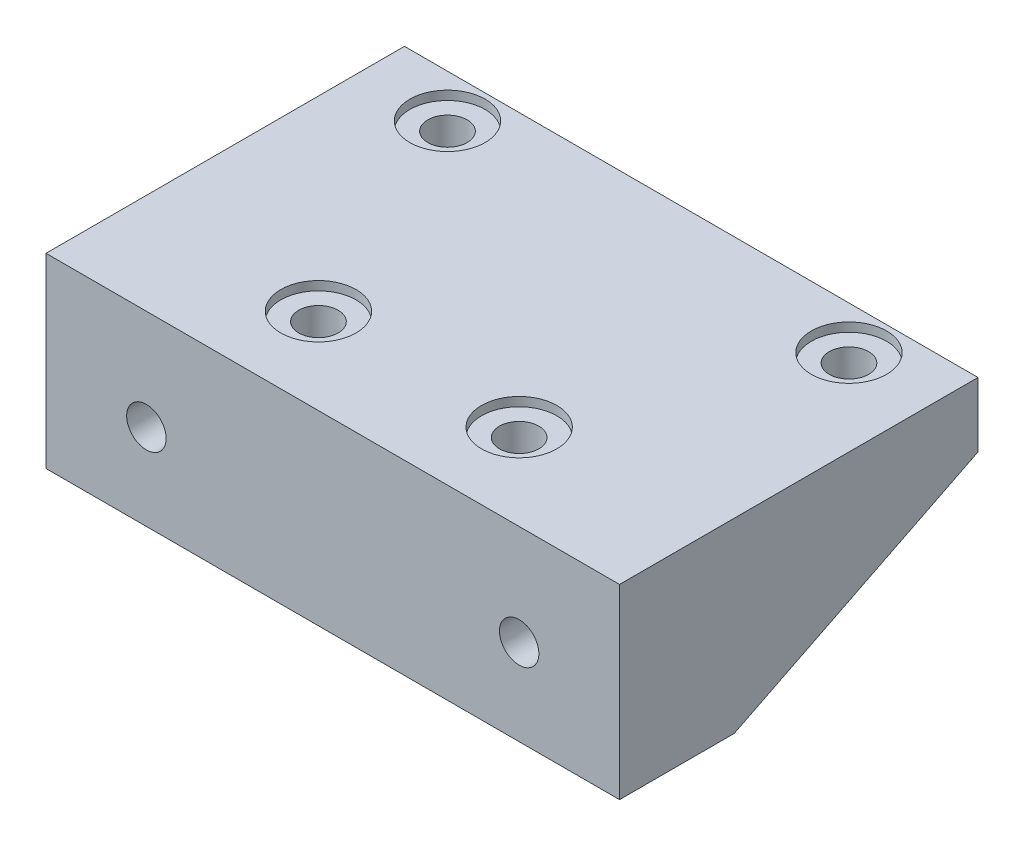
SolidWorks part; units mm, degrees
material "6061-T6 (SS)"
ref_plane "Front Plane" through (0, 0, 0) normal (0, 0, 1) x (1, 0, 0)
ref_plane "Top Plane" through (0, 0, 0) normal (0, 1, 0) x (1, 0, 0)
ref_plane "Right Plane" through (0, 0, 0) normal (1, 0, 0) x (0, 0, -1)
sketch "Sketch1" plane through (0, 0, 0) normal (0, 0, 1) x (1, 0, 0)
  line L1 (0, 0) -> (68, 0)
  line L2 (0, 0) -> (0, 26)
  line L3 (0, 26) -> (68, 26)
  line L4 (68, 0) -> (68, 26)
  dimension "D1" = 68
  dimension "D2" = 26
extrude "Boss-Extrude1" add sketch "Sketch1" along normal blind 6
sketch "Sketch2" plane through (0, 0, 6) normal (0, 0, 1) x (1, 0, 0)
  line L0 (68, 26) -> (0, 26) construction
  line L1 (-6, 26) -> (74, 26)
  line L2 (-6, 26) -> (-6, 20)
  line L3 (-6, 20) -> (74, 20)
  line L4 (74, 26) -> (74, 20)
  line L5 (34, 0) -> (34, 20) construction
  line L6 (0, 0) -> (68, 0) construction
  dimension "D1" = 6
  dimension "D2" = 80
extrude "Boss-Extrude2" add sketch "Sketch2" against normal blind 50
sketch "Sketch3" plane through (0, 0, 0) normal (0, 0, -1) x (-1, 0, 0)
  line L0 (-68, 0) -> (-68, 20) construction
  line L1 (0, 20) -> (0, 0) construction
  line L2 (-60, 12) -> (-8, 12) construction
  line L4 (-68, 20) -> (0, 20) construction
  point P0 (-60, 12)
  point P2 (-8, 12)
  dimension "D1" = 8
  dimension "D2" = 8
  dimension "D3" = 8
hole_wizard "M5 Clearance Hole1" positions "Sketch3" profile "Sketch4" hole size "M5" standard "DIN"
sketch "Sketch4" plane through (60, 12, 0) normal (1, 0, 0) x (0, 1, 0)
  line L0 (0, 0) -> (0, 11.6524)
  line L1 (0, 11.6524) -> (2.75, 10)
  line L2 (2.75, 10) -> (2.75, 0)
  line L5 (2.75, 0) -> (0, 0)
  line L10 (0, 11.6524) -> (-2.75, 10) construction
  line L11 (0, -6.35) -> (0, 107.95) construction
  dimension "Hole Dia." = 5.5
  dimension "Hole Depth" = 10
  dimension "Drill Angle" = 118
sketch "Sketch5" plane through (74, 0, 0) normal (1, 0, 0) x (0, 0, -1)
  line L0 (-6, 0) -> (10, 0)
  line L2 (44, 20) -> (-6, 20)
  line L3 (-6, 20) -> (-6, 0)
  line L4 (44, 20) -> (44, 17)
  line L5 (44, 17) -> (10, 0)
  dimension "D1" = 16
  dimension "D2" = 3
extrude "Boss-Extrude3" add sketch "Sketch5" against normal up to surface (6 mm away) up to face at (68, 10, 3)
extrude "Boss-Extrude4" add sketch "Sketch5<2>" along normal up to surface (-74 mm away) from surface up to face at (0, 10, 3) starting at face at (-6, 23, -19)
sketch "Sketch5<2>" plane through (74, 0, 0) normal (1, 0, 0) x (0, 0, -1) same geometry as "Sketch5"
sketch "Sketch6" plane through (0, 20, 0) normal (0, -1, 0) x (-1, 0, 0)
  line L1 (0, 0) -> (0, 44) construction
  line L2 (-62, 38) -> (-6, 38) construction
  line L4 (0, 44) -> (-68, 44) construction
  line L5 (-20, 6) -> (-48, 6) construction
  line L7 (-34, 6) -> (-34, 0) construction
  line L8 (-68, 0) -> (0, 0) construction
  line L9 (-68, 10) -> (-68, 44) construction
  point P0 (-48, 6)
  point P2 (-20, 6)
  point P4 (-62, 38)
  point P6 (-6, 38)
  dimension "D2" = 6
  dimension "D3" = 6
  dimension "D4" = 28
  dimension "D5" = 6
  dimension "D1" = 6
hole_wizard "M5 Clearance Hole2" positions "Sketch6" profile "Sketch7" hole size "M5" standard "DIN"
sketch "Sketch7" plane through (48, 20, -6) normal (1, 0, 0) x (0, 0, -1)
  line L0 (0, 0) -> (0, 11.6524)
  line L1 (0, 11.6524) -> (2.75, 10)
  line L2 (2.75, 10) -> (2.75, 0)
  line L5 (2.75, 0) -> (0, 0)
  line L10 (0, 11.6524) -> (-2.75, 10) construction
  line L11 (0, -6.35) -> (0, 107.95) construction
  dimension "Hole Dia." = 5.5
  dimension "Hole Depth" = 10
  dimension "Drill Angle" = 118
fillet "Fillet1" radius 2.5 2 edges at (68, 10, 0) (0, 10, 0)
fillet "Fillet2" radius 1 5 edges at (68, 20, -23.25) (67.2678, 20, -0.7322) (34, 20, 0) (0.7322, 20, -0.7322) (0, 20, -23.25)
sketch "Sketch8" plane through (0, 26, 0) normal (0, 1, 0) x (1, 0, 0)
  circle A0 centre (6, 38) radius 5.25
  circle A1 centre (62, 38) radius 5.25
  circle A2 centre (48, 6) radius 5.25
  circle A3 centre (20, 6) radius 5.25
  dimension "D1" = 10.5
extrude "Cut-Extrude1" cut sketch "Sketch8" against normal blind 1.25
equation "\"D2@Sketch3\"=\"D1@Sketch3\""
equation "\"D2@Sketch6\"=\"D1@Sketch6\""
